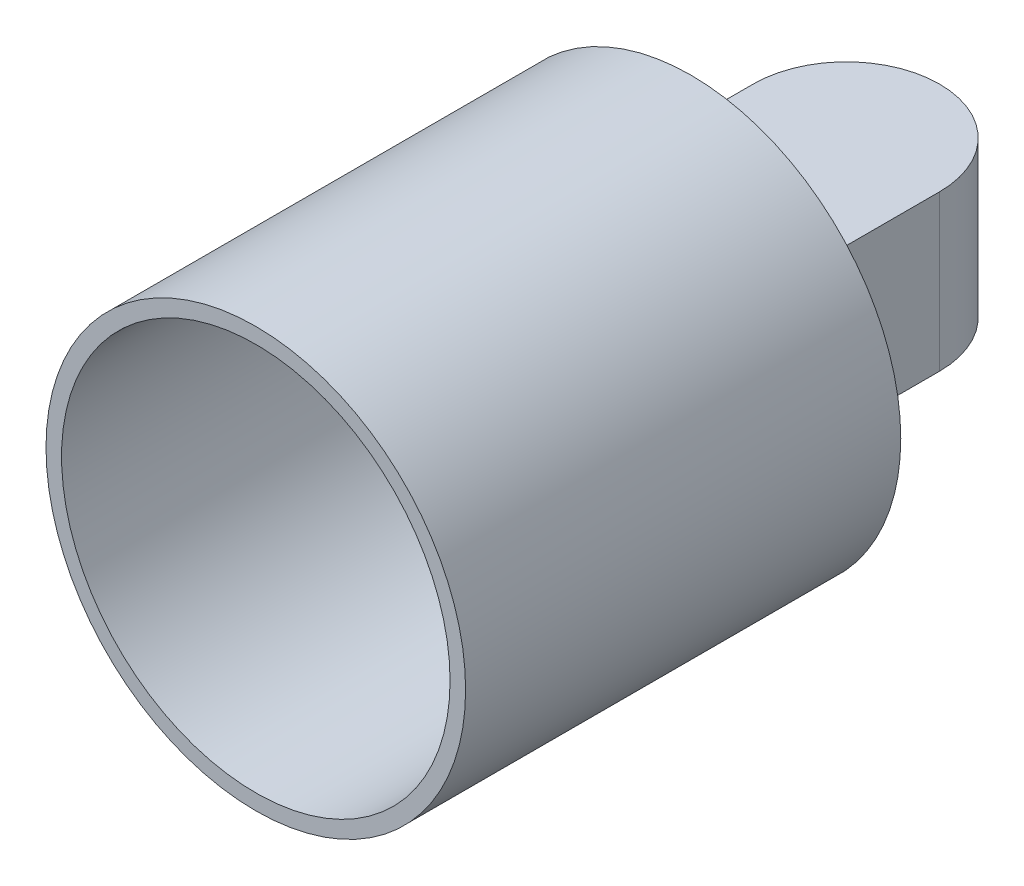
SolidWorks part; units mm, degrees
material "6061 合金"
ref_plane "前视基准面" through (0, 0, 0) normal (0, 0, 1) x (1, 0, 0)
ref_plane "上视基准面" through (0, 0, 0) normal (0, 1, 0) x (1, 0, 0)
ref_plane "右视基准面" through (0, 0, 0) normal (1, 0, 0) x (0, 0, -1)
sketch "草图1" plane through (0, 0, 0) normal (0, 0, 1) x (1, 0, 0)
  circle A0 centre (0, 0) radius 12.5
  circle A1 centre (0, 0) radius 13.5
  dimension "D1" = 25
  dimension "D2" = 1
extrude "凸台-拉伸1" add sketch "草图1" against normal blind 25
sketch "草图2" plane through (0, 0, -25) normal (0, 0, -1) x (-1, 0, 0)
  circle A0 centre (0, 0) radius 13.5
extrude "凸台-拉伸2" add sketch "草图2" along normal blind 3
sketch "草图3" plane through (0, 0, 0) normal (0, 1, 0) x (1, 0, 0)
  line L0 (13.5, 28) -> (-13.5, 28) construction
  line L1 (-6, 28) -> (6, 28)
  line L2 (-6, 28) -> (-6, 38)
  line L4 (6, 28) -> (6, 38)
  line L5 (0, 0) -> (0, 38) construction
  arc A0 (6, 38) -> (-6, 38) centre (0, 38) ccw
  dimension "D1" = 12
  dimension "D2" = 10
extrude "凸台-拉伸3" add sketch "草图3" along normal blind 5 and the other way blind 5
